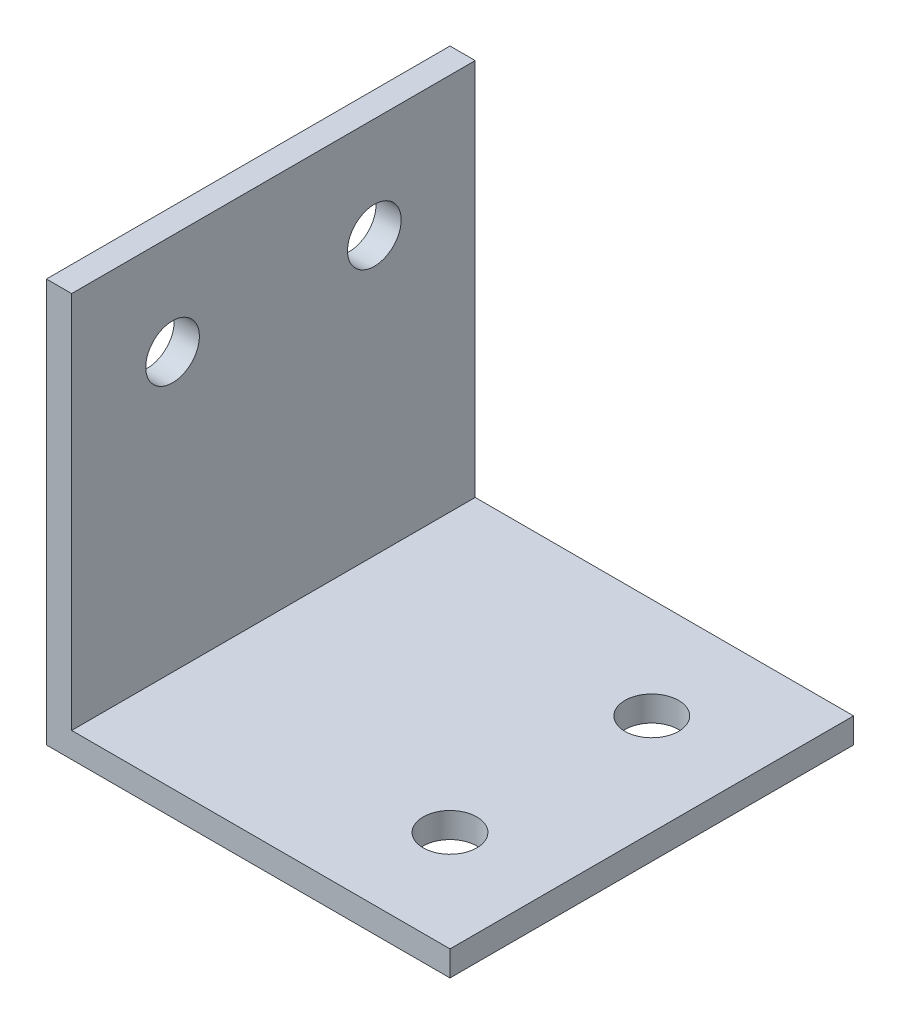
SolidWorks part; units mm, degrees
ref_plane "Front Plane" through (0, 0, 0) normal (0, 0, 1) x (1, 0, 0)
ref_plane "Top Plane" through (0, 0, 0) normal (0, 1, 0) x (1, 0, 0)
ref_plane "Right Plane" through (0, 0, 0) normal (1, 0, 0) x (0, 0, -1)
sketch "Sketch1" plane through (0, 0, 0) normal (0, 0, 1) x (1, 0, 0)
  line L0 (0, 0) -> (0, -50.8)
  line L1 (0, -50.8) -> (50.8, -50.8)
  line L2 (50.8, -50.8) -> (50.8, -47.625)
  line L3 (0, 0) -> (3.175, 0)
  line L4 (3.175, 0) -> (3.175, -47.625)
  line L5 (3.175, -47.625) -> (50.8, -47.625)
  point P3 (50.8, -49.2125)
  dimension "D1" = 3.175
  dimension "D2" = 3.175
  dimension "D3" = 50.8
  dimension "D4" = 50.8
extrude "Boss-Extrude1" add sketch "Sketch1" along normal blind 50.8
hole_wizard "1/4 Clearance Hole1" positions "Sketch3" profile "Sketch2" hole size "1/4" standard "ANSI Inch" end condition up to next
sketch "Sketch3" plane through (0, -47.625, 0) normal (0, 1, 0) x (1, 0, 0)
  line L13 (50.8, 0) -> (3.175, 0) construction
  line L14 (50.8, -50.8) -> (50.8, 0) construction
  point P0 (38.1, -12.7)
  point P43 (38.1, -38.1)
  point P49 (0, 0)
  dimension "D1" = 25.4
  dimension "D2" = 12.7
  dimension "D3" = 12.7
sketch "Sketch2" plane through (38.1, -47.625, 12.7) normal (1, 0, 0) x (0, 0, 1)
  line L0 (0, 0) -> (0, 3.175)
  line L1 (0, 3.175) -> (3.3782, 3.175)
  line L2 (3.3782, 3.175) -> (3.3782, 0)
  line L5 (3.3782, 0) -> (0, 0)
  line L11 (0, -6.35) -> (0, 107.95) construction
  dimension "Thru Hole Dia." = 6.7564
  dimension "Thru Hole Depth" = 3.175
hole_wizard "1/4 Clearance Hole2" positions "Sketch6" profile "Sketch5" hole size "1/4" standard "ANSI Inch" end condition up to next
sketch "Sketch6" plane through (3.175, 0, 0) normal (1, 0, 0) x (0, 0, -1)
  line L5 (-50.8, -47.625) -> (-50.8, 0) construction
  line L6 (-50.8, 0) -> (0, 0) construction
  point P0 (-38.1, -12.7)
  point P18 (-12.7, -12.7)
  point P27 (0, 0)
  dimension "D1" = 25.4
  dimension "D3" = 12.7
  dimension "D4" = 12.7
sketch "Sketch5" plane through (3.175, -12.7, 38.1) normal (0, 1, 0) x (0, 0, -1)
  line L0 (0, 0) -> (0, 3.175)
  line L1 (0, 3.175) -> (3.3782, 3.175)
  line L2 (3.3782, 3.175) -> (3.3782, 0)
  line L5 (3.3782, 0) -> (0, 0)
  line L11 (0, -6.35) -> (0, 107.95) construction
  dimension "Thru Hole Dia." = 6.7564
  dimension "Thru Hole Depth" = 3.175
equation "\".75ibn\"=6.35"
